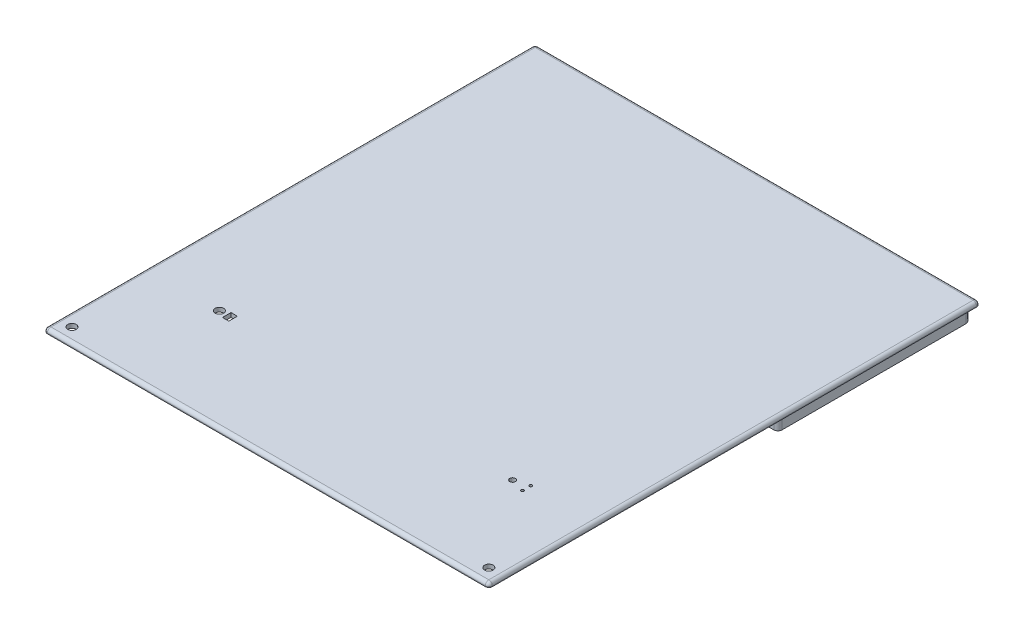
SolidWorks part; units mm, degrees
ref_plane "Front Plane" through (0, 0, 0) normal (0, 0, 1) x (1, 0, 0)
ref_plane "Top Plane" through (0, 0, 0) normal (0, 1, 0) x (1, 0, 0)
ref_plane "Right Plane" through (0, 0, 0) normal (1, 0, 0) x (0, 0, -1)
sketch "Sketch1" plane through (0, 0, 0) normal (0, 1, 0) x (1, 0, 0)
  line L0 (79.25, -36) -> (79.25, 36)
  line L1 (-78, -34.75) -> (78, -34.75)
  line L2 (-78, -34.75) -> (-78, 34.75)
  line L3 (-78, 34.75) -> (78, 34.75)
  line L4 (78, -34.75) -> (78, 34.75)
  line L5 (-78, -34.75) -> (78, 34.75) construction
  line L6 (-78, 34.75) -> (78, -34.75) construction
  line L7 (-79.25, 36) -> (79.25, 36)
  line L8 (-79.25, -36) -> (-79.25, 36)
  line L9 (-78, -36) -> (78, -36)
  line L10 (-78, -36) -> (-78, -86)
  line L11 (-78, -36) -> (78, -36)
  line L12 (-79.25, -36) -> (-79.25, -86)
  line L13 (-79.25, -86) -> (-79.25, -159)
  line L14 (79.25, -36) -> (79.25, -86)
  line L15 (78, -36) -> (78, -86)
  line L16 (-79.25, -36) -> (79.25, -36) construction
  line L17 (-78, -86) -> (-78, -100.5886)
  line L18 (79.25, -86) -> (79.25, -159)
  line L19 (78, -86) -> (78, -157.75)
  line L20 (79.25, -159) -> (-79.25, -159)
  line L21 (78, -159) -> (79.25, -159)
  line L22 (-78, -100.5886) -> (-78, -157.75)
  line L23 (-78, -157.75) -> (78, -157.75)
  line L24 (-78, -157.75) -> (78, -157.75) construction
  line L25 (0, -157.75) -> (0, -117.25)
  line L26 (-40, -117.25) -> (40, -117.25)
  line L27 (-34, -117.25) -> (34, -117.25)
  line L28 (-40, -117.25) -> (-34, -117.25) construction
  circle A0 centre (-37, -117.25) radius 3
  point P0 (0, 0)
  point P27 (0, -117.25)
  point P30 (0, -117.25)
  dimension "D1" = 156
  dimension "D2" = 69.5
  dimension "D4" = 50
  dimension "D5" = 195
  dimension "D6" = 1.25
  dimension "D7" = 40.5
  dimension "D8" = 80
  dimension "D9" = 68
  dimension "D3" = 1.25
sketch "Sketch2" plane through (0, 0, 0) normal (0, 1, 0) x (1, 0, 0)
  line L0 (-79.25, 36) -> (79.25, 36)
  line L1 (79.25, 36) -> (79.25, -159)
  line L2 (79.25, -159) -> (-79.25, -159)
  line L3 (-79.25, -159) -> (-79.25, 36)
extrude "Boss-Extrude1" add sketch "Sketch2" against normal blind 1.25
extrude "Boss-Extrude2" add sketch "Sketch1" along normal blind 105 contours L20 L18 L14 L0 L7 L8 L12 L13 L23 L22 L17 L10 L9 L15 L19 L4 L1 L2 L3 region at (78.9987, 0, 61)
sketch "Sketch4" plane through (0, 0, 0) normal (0, 1, 0) x (1, 0, 0)
  line L0 (-78, -157.75) -> (78, -157.75) construction
  line L1 (0, -157.75) -> (0, -117.75)
  line L2 (0, -7.15) -> (0, 7.15) construction
  line L3 (-34, -117.75) -> (34, -117.75)
  line L4 (-40.15, -117.75) -> (-39.575, -117.75)
  line L5 (-40.15, -117.75) -> (-39.575, -117.75) construction
  line L6 (34, -117.75) -> (34.575, -117.75) construction
  line L7 (-34.575, -117.75) -> (34.575, -117.75)
  line L8 (-34.575, -117.75) -> (-34, -117.75) construction
  line L9 (39.575, -117.75) -> (40.15, -117.75) construction
  line L10 (39.575, -117.75) -> (40.15, -117.75)
  circle A0 centre (-37.075, -117.75) radius 2.5
  circle A1 centre (37.075, -117.75) radius 2.5
  point P12 (0, -117.75)
  point P15 (0, -117.75)
  dimension "D1" = 40
  dimension "D2" = 68
  dimension "D3" = 80.3
extrude "Boss-Extrude3" add sketch "Sketch4" along normal blind 8 contours A0 | A1 region at (37.075, 0, 117.75) region at (-37.075, 0, 117.75)
fillet "Fillet2" radius 2 18 edges at (-78, 0, 0) (0, 0, -34.75) (78, 0, 0) (0, 0, 34.75) (0, 0, 36) (78, 0, 96.875) (0, 0, 157.75) (-78, 0, 96.875) (-37.075, 0, 115.25) (37.075, 0, 115.25) (78, 52.5, -34.75) (-78, 52.5, -34.75) (78, 52.5, 34.75) (-78, 52.5, 34.75) (-78, 52.5, 157.75) (78, 52.5, 157.75) (78, 52.5, 36) (-78, 52.5, 36)
sketch "Sketch5" plane through (0, 0, 36) normal (0, 0, 1) x (1, 0, 0)
  line L0 (-76, 105) -> (76, 105) construction
  line L2 (-76, 105) -> (-76, 2) construction
  line L3 (-58.75, 4.5) -> (58.75, 4.5)
  line L4 (-58.75, 4.5) -> (-58.75, 101.5)
  line L5 (-58.75, 101.5) -> (58.75, 101.5)
  line L6 (58.75, 4.5) -> (58.75, 101.5)
  line L7 (-58.75, 53) -> (58.75, 53)
  line L8 (-53.75, 101.5) -> (-53.75, 98)
  line L14 (-58.75, 98) -> (-53.75, 98)
  line L15 (0, 53) -> (0, 77.907)
  circle A0 centre (-53.75, 98) radius 1.55
  circle A1 centre (-53.75, 8) radius 1.55
  circle A2 centre (53.75, 8) radius 1.55
  circle A3 centre (53.75, 98) radius 1.55
  point P8 (0, 53.5)
  dimension "D1" = 97
  dimension "D2" = 117.5
  dimension "D3" = 17.25
  dimension "D4" = 3.5
  dimension "D5" = 5
  dimension "D6" = 3.5
extrude "Cut-Extrude1" cut sketch "Sketch5" against normal blind 8 contours L14 A0 L8 | L8 A0 L14 | A3 | A1 | A2 region at (-54.4078, 98.6578, 36) region at (-53.5307, 97.7807, 36) region at (-53.75, 8, 36) region at (53.75, 98, 36)
sketch "Sketch6" plane through (0, 0, 157.75) normal (0, 0, -1) x (-1, 0, 0)
  line L0 (-76, 2) -> (76, 2) construction
  line L1 (0, 2) -> (0, 22)
  line L2 (0, 7.15) -> (0, -7.15) construction
  circle A0 centre (0, 22) radius 8.25
  dimension "D1" = 20
extrude "Cut-Extrude2" cut sketch "Sketch6" against normal blind 8 contours A0 region at (-5.6686, 16.3314, 157.75)
sketch "Sketch8" plane through (-79.25, 0, 0) normal (-1, 0, 0) x (0, 0, 1)
  line L0 (159, 55) -> (116.5, 55)
  line L1 (159, -1.25) -> (159, 105) construction
  line L2 (116.5, 5) -> (116.5, 105)
  line L3 (159, 105) -> (-36, 105) construction
  line L4 (116.5, 55) -> (101.5, 55)
  line L5 (116.5, 55) -> (131.5, 55)
  line L7 (113, 58) -> (120, 58)
  line L8 (113, 58) -> (113, 72)
  line L9 (113, 72) -> (120, 72)
  line L10 (120, 58) -> (120, 72)
  line L11 (113, 58) -> (120, 72) construction
  line L12 (113, 72) -> (120, 58) construction
  circle A0 centre (101.5, 55) radius 3
  circle A1 centre (101.5, 65) radius 3
  circle A2 centre (101.5, 75) radius 3
  circle A3 centre (101.5, 85) radius 3
  circle A4 centre (131.5, 55) radius 3.75
  circle A5 centre (131.5, 75) radius 3.75
  point P9 (116.5, 55)
  point P13 (116.5, 65)
  dimension "D4" = 4
  dimension "D5" = 2
  dimension "D1" = 42.5
  dimension "D2" = 15
  dimension "D3" = 15
  dimension "D6" = 7
  dimension "D7" = 14
  dimension "D8" = 10
  dimension "D9" = 50
extrude "Cut-Extrude3" cut sketch "Sketch8" against normal blind 8 contours A0 | A2 | A3 | A1 | A5 | L8 L9 L10 L7 | A4 region at (-79.25, 55, 98.5849) region at (-79.25, 65, 101.5) region at (-79.25, 75, 101.5) region at (-79.25, 85, 101.5) region at (-79.25, 75, 131.5)
fillet "Fillet3" radius 1.25 4 edges at (0, -1.25, 159) (79.25, -1.25, 61.5) (0, -1.25, -36) (-79.25, -1.25, 61.5)
fillet "Fillet4" radius 1.25 8 edges at (-78.8839, -0.8839, 158.6339) (78.8839, -0.8839, 158.6339) (78.8839, -0.8839, -35.6339) (-78.8839, -0.8839, -35.6339) (-79.25, 52.5, 159) (79.25, 52.5, 159) (79.25, 52.5, -36) (-79.25, 52.5, -36)
sketch "Sketch11" plane through (79.25, 0, 0) normal (1, 0, 0) x (0, 0, -1)
  line L0 (-157.75, 105) -> (34.75, 0) construction
  line L1 (34.75, 105) -> (-157.75, 0)
  line L2 (87.175, 0) -> (-87.175, 0) construction
  line L4 (-111.5, 102.5) -> (-11.5, 102.5)
  line L5 (-111.5, 102.5) -> (-111.5, 2.5)
  line L6 (-111.5, 2.5) -> (-11.5, 2.5)
  line L7 (-11.5, 102.5) -> (-11.5, 2.5)
  line L8 (-111.5, 102.5) -> (-11.5, 2.5) construction
  line L9 (-111.5, 2.5) -> (-11.5, 102.5) construction
  line L10 (-99, 15) -> (-24, 15)
  line L11 (-99, 15) -> (-99, 90)
  line L12 (-99, 90) -> (-24, 90)
  line L13 (-24, 15) -> (-24, 90)
  line L14 (-99, 15) -> (-24, 90) construction
  line L15 (-99, 90) -> (-24, 15) construction
  circle A0 centre (-11.5, 102.5) radius 1.55
  circle A1 centre (-111.5, 102.5) radius 1.55
  circle A2 centre (-99, 90) radius 1.55
  circle A3 centre (-24, 90) radius 1.55
  circle A4 centre (-99, 15) radius 1.55
  circle A5 centre (-111.5, 2.5) radius 1.55
  circle A6 centre (-11.5, 2.5) radius 1.55
  circle A7 centre (-24, 15) radius 1.55
  point P9 (-61.5, 52.5)
  point P14 (-61.5, 52.5)
  dimension "D1" = 100
  dimension "D2" = 100
  dimension "D3" = 75
  dimension "D4" = 75
extrude "Cut-Extrude4" cut sketch "Sketch11" against normal blind 8 contours L7 A0 L4 | L4 A0 L7 | L13 A3 L12 | L12 A3 L13 | L6 A6 L7 | L5 A5 L6 | L6 A5 L5 | L11 A4 L10 | L10 A4 L11 | L10 A7 L13 | L13 A7 L10 | A1 | A2 | A6 region at (79.25, 101.8422, 12.1578) region at (79.25, 102.7193, 11.2807) region at (79.25, 2.2807, 11.2807) region at (79.25, 14.7807, 23.7807) region at (79.25, 15.6578, 24.6578) region at (79.25, 89.3422, 24.6578) region at (79.25, 90.2193, 23.7807) region at (79.25, 15.6578, 98.3422) region at (79.25, 14.7807, 99.2193) region at (79.25, 2.2807, 111.7193) region at (79.25, 3.1578, 110.8422)
sketch "Sketch12" plane through (0, 105, 0) normal (0, 1, 0) x (1, 0, 0)
  line L0 (0, -155.75) -> (0, -144.3132)
  line L1 (-78, -157.75) -> (-73, -157.75)
  line L2 (-78, -157.75) -> (-78, -152.75)
  line L3 (-78, -152.75) -> (-73, -152.75)
  line L4 (-73, -157.75) -> (-73, -152.75)
  line L5 (-76, -155.75) -> (76, -155.75) construction
  line L6 (0, -7.15) -> (0, 7.15) construction
  line L7 (78, -152.75) -> (73, -152.75)
  line L8 (73, -157.75) -> (73, -152.75)
  line L9 (78, -157.75) -> (73, -157.75)
  line L10 (78, -157.75) -> (78, -152.75)
  line M6 (76, -157.75) -> (-76, -157.75)
  arc M7 (-76, -157.75) -> (-78, -155.75) centre (-76, -155.75) cw
  line M8 (-78, -155.75) -> (-78, -38)
  line M12 (78, -38) -> (78, -155.75)
  arc M13 (78, -155.75) -> (76, -157.75) centre (76, -155.75) cw
  dimension "D1" = 5
  dimension "D2" = 5
extrude "Boss-Extrude5" add sketch "Sketch12" against normal up to surface (105 mm away) contours L8 L7 M6 M13 M12 | L4 L3 M6 M8 M7 region at (75.427, 105, 155.177) region at (-75.427, 105, 155.177) up to face at (0, 0, 96.875)
fillet "Fillet5" radius 1.25 14 edges at (78, 53.5, 152.75) (77.4142, 0.5858, 152.75) (74.5, 0, 152.75) (73, 0, 154.25) (73, 0.5858, 157.1642) (-73, 0, 154.25) (-73, 0.5858, 157.1642) (-74.5, 0, 152.75) (-77.4142, 0.5858, 152.75) (73, 53.5, 157.75) (73, 52.5, 152.75) (-73, 53.5, 157.75) (-78, 53.5, 152.75) (-73, 52.5, 152.75)
sketch "Sketch14" plane through (0, 105, 0) normal (0, 1, 0) x (1, 0, 0)
  line L0 (78, -38) -> (78, -151.5) construction
  line L1 (73.3661, -153.1161) -> (78, -153.1161)
  line L2 (73.3661, -153.1161) -> (73.3661, -157.75)
  line L3 (73.3661, -157.75) -> (78, -157.75)
  line L4 (78, -153.1161) -> (78, -157.75)
  line L5 (73.3661, -153.1161) -> (78, -157.75) construction
  line L6 (78, -157.75) -> (78.0536, -157.7607) construction
  line L7 (0, -157.75) -> (0, -147.0716)
  line L8 (-71.75, -157.75) -> (71.75, -157.75) construction
  line L9 (0, -7.15) -> (0, 7.15) construction
  arc A0 (74.25, -152.75) -> (73, -154) centre (74.25, -154) ccw construction
  circle A1 centre (75.6831, -155.4331) radius 1.525
  circle A2 centre (-75.6831, -155.4331) radius 1.525
extrude "Cut-Extrude5" cut sketch "Sketch14" against normal blind 8 contours A1 | A2 region at (75.6831, 105, 155.4331) region at (-75.6831, 105, 155.4331)
sketch "Sketch15" plane through (0, 105, 0) normal (0, 1, 0) x (1, 0, 0)
  line L16 (76, 33) -> (-76, 33)
  line L17 (-76.25, 32.75) -> (-76.25, -32.75)
  line L18 (-76, -33) -> (76, -33)
  line L19 (76.25, -32.75) -> (76.25, 32.75)
  line L20 (-77.5, 32.75) -> (-77.5, -32.75)
  line L21 (-76, -34.25) -> (76, -34.25)
  line L22 (77.5, -32.75) -> (77.5, 32.75)
  line L23 (76, 34.25) -> (-76, 34.25)
  line L24 (-77.5, 32.75) -> (-77.5, -32.75)
  line L25 (-76, -34.25) -> (76, -34.25)
  line L26 (77.5, -32.75) -> (77.5, 32.75)
  line L27 (76, 34.25) -> (-76, 34.25)
  arc A17 (-76, 33) -> (-76.25, 32.75) centre (-76, 32.75) ccw
  arc A18 (-76.25, -32.75) -> (-76, -33) centre (-76, -32.75) ccw
  arc A19 (76, -33) -> (76.25, -32.75) centre (76, -32.75) ccw
  arc A20 (76.25, 32.75) -> (76, 33) centre (76, 32.75) ccw
  arc A21 (-76, 34.25) -> (-77.5, 32.75) centre (-76, 32.75) ccw
  arc A22 (-77.5, -32.75) -> (-76, -34.25) centre (-76, -32.75) ccw
  arc A23 (76, -34.25) -> (77.5, -32.75) centre (76, -32.75) ccw
  arc A24 (77.5, 32.75) -> (76, 34.25) centre (76, 32.75) ccw
  arc A25 (-76, 34.25) -> (-77.5, 32.75) centre (-76, 32.75) ccw
  arc A26 (-77.5, -32.75) -> (-76, -34.25) centre (-76, -32.75) ccw
  arc A27 (76, -34.25) -> (77.5, -32.75) centre (76, -32.75) ccw
  arc A28 (77.5, 32.75) -> (76, 34.25) centre (76, 32.75) ccw
  dimension "D1" = 0.5
  dimension "D2" = 1.25
extrude "Boss-Extrude6" add sketch "Sketch15" against normal blind 5 separate body
sketch "Sketch19" plane through (0, 105, 0) normal (0, 1, 0) x (1, 0, 0)
  circle A2 centre (75.6831, -155.4331) radius 1.525
  circle A3 centre (75.6831, -155.4331) radius 1.525
  circle A5 centre (-75.6831, -155.4331) radius 1.525
  circle A6 centre (-75.6831, -155.4331) radius 1.525
  dimension "D1" = 0
  dimension "D2" = 0
extrude "Cut-Extrude10" cut sketch "Sketch19" along normal blind 176.5 and the other way blind 9
sketch "Sketch16" plane through (0, 105, 0) normal (0, 1, 0) x (1, 0, 0)
  line L8 (-79.25, 34.75) -> (-79.25, -157.75)
  line L9 (-78, -159) -> (78, -159)
  line L10 (79.25, -157.75) -> (79.25, 34.75)
  line L11 (78, 36) -> (-78, 36)
  line L12 (-79.25, 34.75) -> (-79.25, -157.75)
  line L13 (-78, -159) -> (78, -159)
  line L14 (79.25, -157.75) -> (79.25, 34.75)
  line L15 (78, 36) -> (-78, 36)
  arc A8 (-79.25, -157.75) -> (-78, -159) centre (-78, -157.75) ccw
  arc A9 (78, -159) -> (79.25, -157.75) centre (78, -157.75) ccw
  arc A10 (79.25, 34.75) -> (78, 36) centre (78, 34.75) ccw
  arc A11 (-78, 36) -> (-79.25, 34.75) centre (-78, 34.75) ccw
  arc A12 (-79.25, -157.75) -> (-78, -159) centre (-78, -157.75) ccw
  arc A13 (78, -159) -> (79.25, -157.75) centre (78, -157.75) ccw
  arc A14 (79.25, 34.75) -> (78, 36) centre (78, 34.75) ccw
  arc A15 (-78, 36) -> (-79.25, 34.75) centre (-78, 34.75) ccw
  dimension "D1" = 0
extrude "Boss-Extrude7" add sketch "Sketch16" along normal blind 1.5
sketch "Sketch17" plane through (0, 105, 0) normal (0, -1, 0) x (1, 0, 0)
  line L5 (97.501, -101.5148) -> (-116.8928, -101.5148)
  line L6 (97.501, -101.5148) -> (97.501, 210.2358)
  line L7 (97.501, 210.2358) -> (-116.8928, 210.2358)
  line L8 (78, -32.75) -> (78, 32.75)
  line L9 (76, 34.75) -> (-76, 34.75)
  line L10 (-78, 32.75) -> (-78, -32.75)
  line L11 (-76, -34.75) -> (76, -34.75)
  line L12 (78, -32.75) -> (78, 32.75)
  line L13 (76, 34.75) -> (-76, 34.75)
  line L14 (-78, 32.75) -> (-78, -32.75)
  line L15 (-76, -34.75) -> (76, -34.75)
  line L16 (-116.8928, -101.5148) -> (-116.8928, 210.2358)
  line L17 (97.501, -101.5148) -> (-116.8928, 210.2358) construction
  line L18 (97.501, 210.2358) -> (-116.8928, -101.5148) construction
  arc A8 (78, 32.75) -> (76, 34.75) centre (76, 32.75) ccw
  arc A9 (-76, 34.75) -> (-78, 32.75) centre (-76, 32.75) ccw
  arc A10 (-78, -32.75) -> (-76, -34.75) centre (-76, -32.75) ccw
  arc A11 (76, -34.75) -> (78, -32.75) centre (76, -32.75) ccw
  arc A12 (78, 32.75) -> (76, 34.75) centre (76, 32.75) ccw
  arc A13 (-76, 34.75) -> (-78, 32.75) centre (-76, 32.75) ccw
  arc A14 (-78, -32.75) -> (-76, -34.75) centre (-76, -32.75) ccw
  arc A15 (76, -34.75) -> (78, -32.75) centre (76, -32.75) ccw
  point P2 (-9.6959, 54.3605)
  dimension "D1" = 0
extrude "Cut-Extrude6" cut sketch "Sketch17" along normal blind 142.5
sketch "Sketch18" plane through (0, 100, 0) normal (0, -1, 0) x (1, 0, 0)
  line L1 (-421.9306, -105.0953) -> (421.9306, -105.0953)
  line L2 (-421.9306, -105.0953) -> (-421.9306, 105.0953)
  line L3 (-421.9306, 105.0953) -> (421.9306, 105.0953)
  line L4 (421.9306, -105.0953) -> (421.9306, 105.0953)
  line L5 (-421.9306, -105.0953) -> (421.9306, 105.0953) construction
  line L6 (-421.9306, 105.0953) -> (421.9306, -105.0953) construction
  point P0 (0, 0)
extrude "Cut-Extrude7" cut sketch "Sketch18" along normal blind 211.5
fillet "Fillet6" radius 1.25 8 edges at (0, 106.5, -36) (78.8839, 106.5, -35.6339) (79.25, 106.5, 61.5) (78.8839, 106.5, 158.6339) (0, 106.5, 159) (-78.8839, 106.5, 158.6339) (-79.25, 106.5, 61.5) (-78.8839, 106.5, -35.6339)
sketch "Sketch21" plane through (0, 106.5, 0) normal (0, 1, 0) x (1, 0, 0)
  line L0 (-78.8839, -158.6339) -> (-75.6807, -155.4307)
  line L1 (0, -159) -> (0, -145.5027)
  line L2 (78, -159) -> (-78, -159) construction
  line L3 (0, -7.15) -> (0, 7.15) construction
  arc A0 (-79.25, -157.75) -> (-78, -159) centre (-78, -157.75) ccw construction
  circle A1 centre (-75.6807, -155.4307) radius 1.525
  circle A2 centre (75.6807, -155.4307) radius 1.525
  dimension "D1" = 4.53
extrude "Cut-Extrude11" cut sketch "Sketch21" against normal blind 46.5 contours A1 | A2
sketch "Sketch22" plane through (0, 106.5, 0) normal (0, 1, 0) x (1, 0, 0)
  line L0 (53, -122.75) -> (-53, -122.75)
  line L1 (-78, -157.75) -> (-53, -157.75)
  line L2 (-78, -157.75) -> (-78, -122.75)
  line L3 (-78, -122.75) -> (-53, -122.75)
  line L4 (-53, -157.75) -> (-53, -122.75)
  line L6 (53, -124.25) -> (53, -121.25)
  line L7 (53, -122.75) -> (48, -122.75)
  circle A0 centre (-53, -122.75) radius 1.525
  circle A1 centre (53, -121.25) radius 0.5
  circle A2 centre (53, -124.25) radius 0.5
  circle A3 centre (48, -122.75) radius 1
  point P9 (0, -122.75)
  point P11 (53, -122.75)
  dimension "D3" = 3
  dimension "D4" = 5
  dimension "D1" = 25
  dimension "D2" = 35
extrude "Cut-Extrude12" cut sketch "Sketch22" against normal blind 46.5 contours L3 A0 L4 | L4 A0 L3 | A2 | A1 | L7 A3 L0 | L0 A3 L7 | L4 A0 L0 region at (-52.3528, 106.5, 123.3972) region at (-53, 106.5, 122.1028) region at (48, 106.5, 123.1744) region at (48, 106.5, 122.3256) region at (53.3436, 106.5, 123.9064) region at (52.6564, 106.5, 120.9064) region at (-53.6472, 106.5, 123.3972)
sketch "Sketch23" plane through (0, 105, 0) normal (0, -1, 0) x (1, 0, 0)
  line L1 (-106.4259, 59.8786) -> (117.9234, 59.8786)
  line L2 (-106.4259, 59.8786) -> (-106.4259, 79.8786)
  line L3 (-106.4259, 79.8786) -> (117.9234, 79.8786)
  line L4 (117.9234, 59.8786) -> (117.9234, 79.8786)
  dimension "D1" = 20
extrude "Cut-Extrude13" cut sketch "Sketch23" against normal blind 108
sketch "Sketch24" plane through (0, 0, 79.8786) normal (0, 0, -1) x (-1, 0, 0)
  line L0 (-76, 105) -> (76, 105) construction
  line L1 (-118.449, 63.4) -> (105.3789, 63.4)
  line L2 (-118.449, 63.4) -> (-118.449, 146.6)
  line L3 (-118.449, 146.6) -> (105.3789, 146.6)
  line L4 (105.3789, 63.4) -> (105.3789, 146.6)
  line L5 (-118.449, 63.4) -> (105.3789, 146.6) construction
  line L6 (-118.449, 146.6) -> (105.3789, 63.4) construction
  point P0 (-6.535, 105)
extrude "Cut-Extrude14" cut sketch "Sketch24" against normal blind 108
sketch "Sketch25" plane through (0, 0, 59.8786) normal (0, 0, 1) x (1, 0, 0)
  line L8 (79.25, 105) -> (79.25, 105.25)
  line L9 (78, 106.5) -> (-78, 106.5)
  line L10 (-79.25, 105.25) -> (-79.25, 105)
  line L11 (-79.25, 105) -> (79.25, 105)
  line L12 (79.25, 105) -> (79.25, 105.25)
  line L13 (78, 106.5) -> (-78, 106.5)
  line L14 (-79.25, 105.25) -> (-79.25, 105)
  line L15 (-79.25, 105) -> (79.25, 105)
  arc A4 (79.25, 105.25) -> (78, 106.5) centre (78, 105.25) ccw
  arc A5 (-78, 106.5) -> (-79.25, 105.25) centre (-78, 105.25) ccw
  arc A6 (79.25, 105.25) -> (78, 106.5) centre (78, 105.25) ccw
  arc A7 (-78, 106.5) -> (-79.25, 105.25) centre (-78, 105.25) ccw
  dimension "D1" = 0
extrude "Boss-Extrude8" add sketch "Sketch25" along normal blind 79.12
fillet "Fillet7" radius 1.25 5 edges at (79.25, 105.125, 138.9986) (78.8839, 106.1339, 138.9986) (-79.25, 105.125, 138.9986) (-78.8839, 106.1339, 138.9986) (0, 106.5, 138.9986)
sketch "Sketch27" plane through (0, 106.5, 0) normal (0, 1, 0) x (1, 0, 0)
  line L0 (-78, -102.7486) -> (-53, -102.7486)
  line L1 (-78, 34.75) -> (-78, -137.7486) construction
  line L2 (-53, -102.7486) -> (-53, -137.7486)
  line L3 (-78, -137.7486) -> (78, -137.7486) construction
  line L4 (78, -102.7486) -> (51.437, -102.7486)
  line L5 (-50.3758, -104.2736) -> (-48.1242, -104.2736)
  line L6 (-50.3758, -104.2736) -> (-50.3758, -101.2236)
  line L7 (-50.3758, -101.2236) -> (-48.1242, -101.2236)
  line L8 (-48.1242, -104.2736) -> (-48.1242, -101.2236)
  line L9 (-50.3758, -104.2736) -> (-48.1242, -101.2236) construction
  line L10 (-50.3758, -101.2236) -> (-48.1242, -104.2736) construction
  line L11 (78, -137.7486) -> (78, 34.75) construction
  line L12 (56.437, -102.7486) -> (56.437, -101.2486)
  line L13 (56.437, -101.2486) -> (56.437, -104.2486)
  circle A0 centre (-53, -102.7486) radius 1.525
  circle A1 centre (51.437, -102.7486) radius 1
  circle A2 centre (56.437, -101.2486) radius 0.5
  circle A3 centre (56.437, -104.2486) radius 0.5
  point P8 (-49.25, -102.7486)
  dimension "D3" = 3.75
  dimension "D4" = 1.5
  dimension "D1" = 35
  dimension "D2" = 25
  dimension "D5" = 3
  dimension "D6" = 26.563
  dimension "D7" = 5
extrude "Cut-Extrude16" cut sketch "Sketch27" against normal blind 79.12 contours L5 L8 L7 L6 | L0 A0 L2 | L2 A0 L0 | A3 | A2 | A1 region at (-52.7843, 106.5, 102.5328) region at (-53.6472, 106.5, 103.3958) region at (50.4653, 106.5, 102.7486) region at (56.0935, 106.5, 100.905) region at (56.7806, 106.5, 103.905) region at (-49.25, 106.5, 102.7486)
sketch "Sketch28" plane through (0, 106.5, 0) normal (0, 1, 0) x (1, 0, 0)
  line L0 (-79.25, -137.2818) -> (-79.25, -139.6014)
  line L1 (-79.25, -137.7486) -> (-79.25, 34.75) construction
  line L2 (-79.25, -139.6014) -> (-76.5397, -138.9986)
  line L3 (78, -138.9986) -> (-78, -138.9986) construction
  line L4 (-76.5397, -138.9986) -> (-81.3494, -138.9986)
  line L5 (0, -137.7486) -> (0, -133.4174)
  line L6 (-79.25, -138.9986) -> (-74.25, -138.9986)
  line L7 (-79.25, -138.9986) -> (-79.25, -133.9986)
  line L8 (-79.25, -133.9986) -> (-74.25, -133.9986)
  line L9 (-74.25, -138.9986) -> (-74.25, -133.9986)
  line L10 (-78, -137.7486) -> (78, -137.7486) construction
  line L11 (0, -3.575) -> (0, 3.575) construction
  circle A0 centre (-74.25, -133.9986) radius 1.525
  circle A1 centre (74.25, -133.9986) radius 1.525
  dimension "D1" = 5
  dimension "D2" = 5
extrude "Cut-Extrude17" cut sketch "Sketch28" against normal blind 79.12 contours L9 A0 L8 | L8 A0 L9 | A1 region at (-74.0343, 106.5, 133.7828) region at (-74.8972, 106.5, 134.6458) region at (74.25, 106.5, 133.9986)
